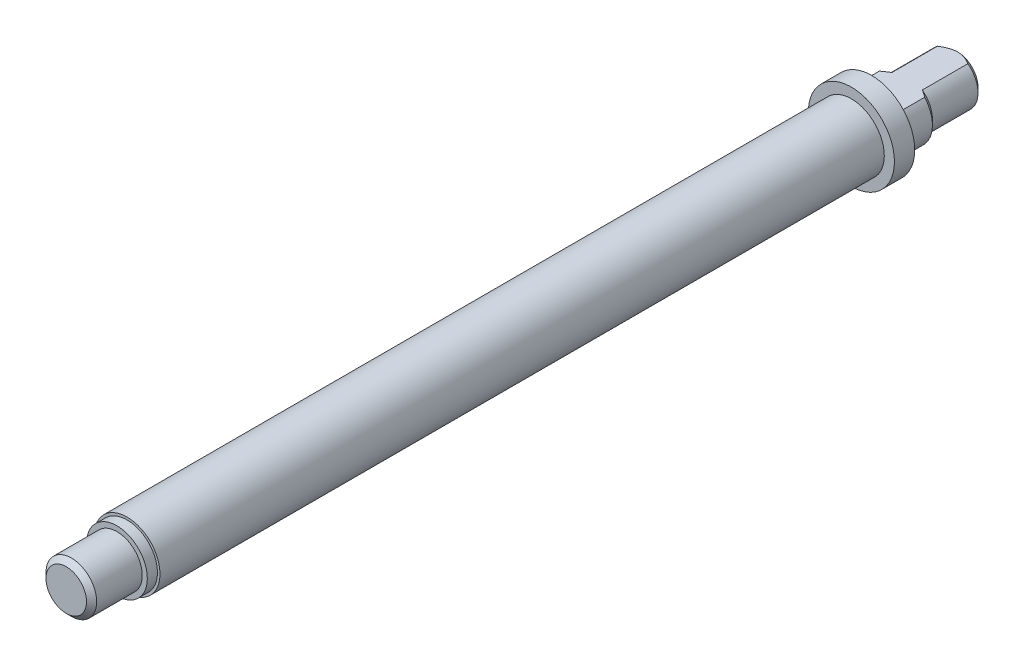
SolidWorks part; units mm, degrees
material "7075-O (SS)"
ref_plane "前视基准面" through (0, 0, 0) normal (0, 0, 1) x (1, 0, 0)
ref_plane "上视基准面" through (0, 0, 0) normal (0, 1, 0) x (1, 0, 0)
ref_plane "右视基准面" through (0, 0, 0) normal (1, 0, 0) x (0, 0, -1)
sketch "草图1" plane through (0, 0, 0) normal (0, 0, 1) x (1, 0, 0)
  circle A0 centre (0, 0) radius 4.25
  dimension "D1" = 8.5
extrude "拉伸1" add sketch "草图1" along normal mid plane 73.5
sketch "草图2" plane through (0, 0, 36.75) normal (0, 0, 1) x (1, 0, 0)
  circle A0 centre (0, 0) radius 3
  dimension "D1" = 6
extrude "拉伸2" add sketch "草图2" along normal blind 1
sketch "草图3" plane through (0, 0, 37.75) normal (0, 0, 1) x (1, 0, 0)
  circle A0 centre (0, 0) radius 2.5
  dimension "D1" = 5
extrude "拉伸3" add sketch "草图3" along normal blind 5
sketch "草图4" plane through (0, 0, -36.75) normal (0, 0, -1) x (-1, 0, 0)
  circle A0 centre (0, 0) radius 3
  dimension "D1" = 6
extrude "拉伸4" add sketch "草图4" along normal blind 3.5
sketch "草图5" plane through (0, 0, -40.25) normal (0, 0, -1) x (-1, 0, 0)
  circle A0 centre (0, 0) radius 2.5
  dimension "D1" = 5
extrude "拉伸5" add sketch "草图5" along normal blind 5
chamfer "倒角1" distance 0.5 angle 45 2 edges at (-2.5, 0, -45.25) (2.5, 0, 42.75)
chamfer "倒角2" distance 0.5 angle 45 1 edges at (-3, 0, -40.25)
sketch "草图6" plane through (0, 0, -45.25) normal (0, 0, -1) x (-1, 0, 0)
  line L0 (0, 0) -> (0, 2) construction
  line L1 (-3, 5) -> (3, 5)
  line L2 (-3, 5) -> (-3, 2)
  line L3 (-3, 2) -> (3, 2)
  line L4 (3, 5) -> (3, 2)
  dimension "D1" = 2
  dimension "D2" = 3
  dimension "D3" = 6
extrude "拉伸6" cut sketch "草图6" against normal up to surface (8.5 mm away) up to face at (4.25, 0, -36.75)
sketch "草图7" plane through (0, 0, 36.75) normal (0, 0, 1) x (1, 0, 0)
  circle A0 centre (0, 0) radius 3.25
  circle A1 centre (0, 0) radius 4.25
extrude "切除-拉伸1" cut sketch "草图7" against normal blind 71.5
